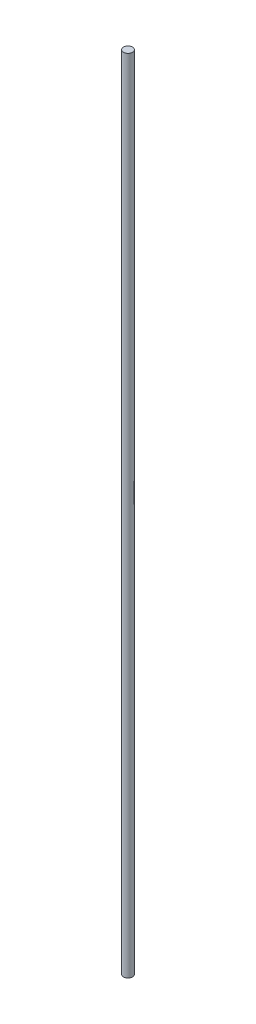
SolidWorks part; units mm, degrees
ref_plane "Front Plane" through (0, 0, 0) normal (0, 0, 1) x (1, 0, 0)
ref_plane "Top Plane" through (0, 0, 0) normal (0, 1, 0) x (1, 0, 0)
ref_plane "Right Plane" through (0, 0, 0) normal (1, 0, 0) x (0, 0, -1)
sketch "Sketch1" plane through (0, 0, 0) normal (0, 1, 0) x (1, 0, 0)
  circle A0 centre (0, 0) radius 5.08
extrude "Boss-Extrude1" add sketch "Sketch1" along normal blind 900.684
